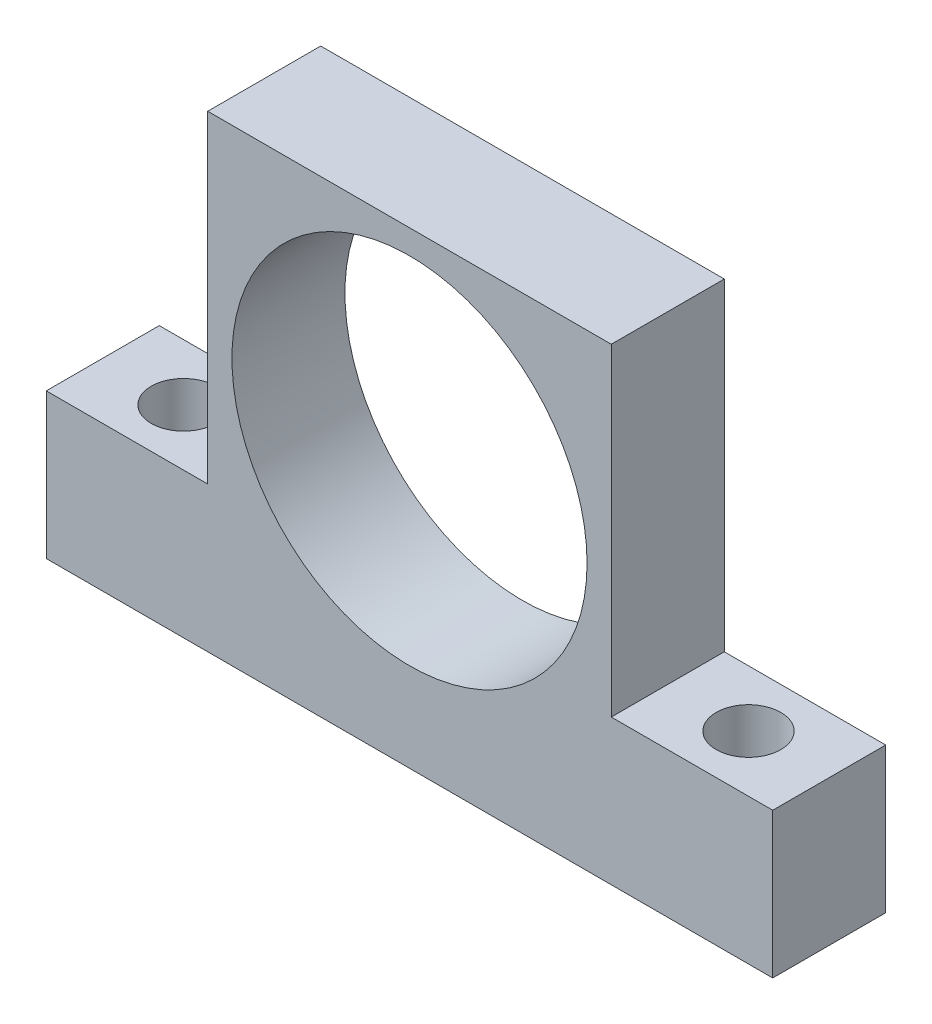
SolidWorks part; units mm, degrees
material "ABS"
ref_plane "Front Plane" through (0, 0, 0) normal (0, 0, 1) x (1, 0, 0)
ref_plane "Top Plane" through (0, 0, 0) normal (0, 1, 0) x (1, 0, 0)
ref_plane "Right Plane" through (0, 0, 0) normal (1, 0, 0) x (0, 0, -1)
sketch "Sketch1" plane through (0, 0, 0) normal (0, 0, 1) x (1, 0, 0)
  line L1 (-12.5, 12.5) -> (12.5, 12.5)
  line L2 (-12.5, 12.5) -> (-12.5, -16.5)
  line L3 (-12.5, -16.5) -> (12.5, -16.5)
  line L4 (12.5, 12.5) -> (12.5, -16.5)
  line L5 (-12.5, 12.5) -> (12.5, -16.5) construction
  line L6 (-12.5, -16.5) -> (12.5, 12.5) construction
  line L7 (12.5, -16.5) -> (22.5, -16.5)
  line L8 (12.5, -16.5) -> (12.5, -7.5)
  line L9 (12.5, -7.5) -> (22.5, -7.5)
  line L10 (22.5, -16.5) -> (22.5, -7.5)
  line L11 (12.5, -16.5) -> (22.5, -7.5) construction
  line L12 (12.5, -7.5) -> (22.5, -16.5) construction
  line L13 (-12.5, -16.5) -> (-22.5, -16.5)
  line L14 (-12.5, -16.5) -> (-12.5, -7.5)
  line L15 (-12.5, -7.5) -> (-22.5, -7.5)
  line L16 (-22.5, -16.5) -> (-22.5, -7.5)
  line L17 (-12.5, -16.5) -> (-22.5, -7.5) construction
  line L18 (-12.5, -7.5) -> (-22.5, -16.5) construction
  circle A0 centre (0, 0) radius 4.1
  circle A1 centre (0, 0) radius 11
  point P8 (0, 0)
  point P14 (17.5, -12)
  point P16 (-17.5, -12)
  dimension "D4" = 8.2
  dimension "D5" = 22
  dimension "D1" = 12.5
  dimension "D2" = 29
  dimension "D3" = 25
  dimension "D6" = 10
  dimension "D7" = 9
  dimension "D8" = 10
  dimension "D9" = 9
  dimension "D10" = 12.5
extrude "Boss-Extrude1" add sketch "Sketch1" along normal blind 7 contours L4 L1 L2 L3 A1 | L16 L13 L2 L15 | L7 L10 L9 L4 region at (0, 12.1171, 0) region at (-17.5, -12, 0) region at (17.5, -12, 0)
sketch "Sketch2" plane through (0, -7.5, 0) normal (0, 1, 0) x (1, 0, 0)
  line L0 (-22.5, 0) -> (-12.5, -7)
  line L1 (-12.5, -7) -> (-22.5, -7)
  line L2 (-22.5, -7) -> (-12.5, 0)
  line L3 (12.5, 0) -> (22.5, -7)
  line L4 (22.5, -7) -> (22.5, 0)
  line L5 (22.5, 0) -> (12.5, -7)
  circle A0 centre (-17.5, -3.5) radius 2
  circle A1 centre (17.5, -3.5) radius 2
  dimension "D1" = 4
  dimension "D2" = 4
extrude "Cut-Extrude1" cut sketch "Sketch2" against normal blind 9 contours L0 A0 L2 | L2 A0 L0 | L0 A0 L2 | L2 A0 L0 | A1 region at (-17.5, -7.5, 2.3623) region at (-18.752, -7.5, 3.5) region at (-16.248, -7.5, 3.5) region at (-17.5, -7.5, 4.6377)
